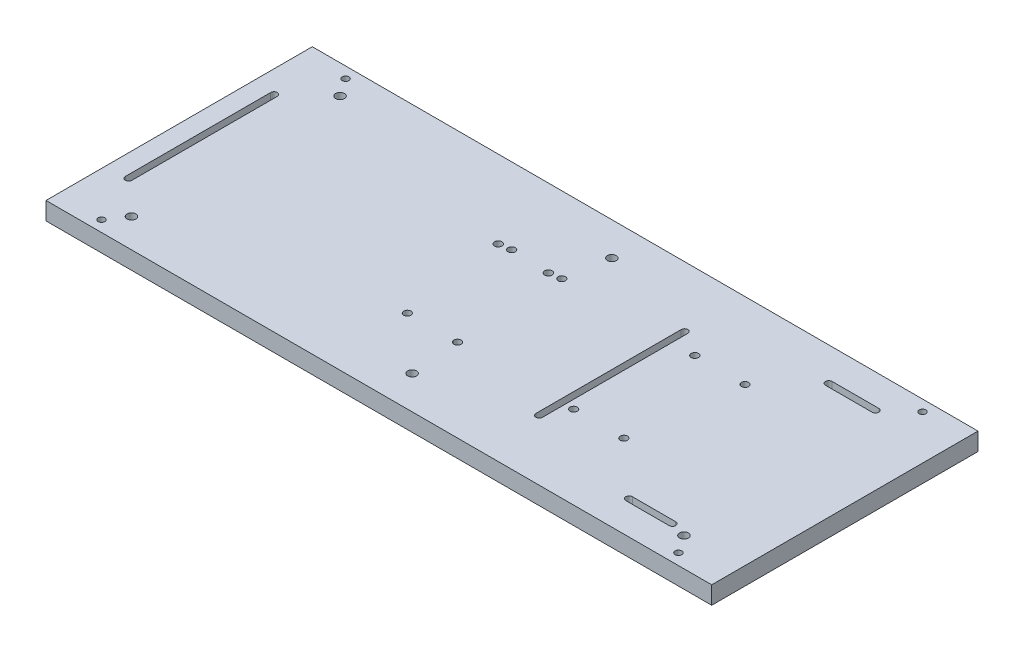
SolidWorks part; units mm, degrees
ref_plane "Front Plane" through (0, 0, 0) normal (0, 0, 1) x (1, 0, 0)
ref_plane "Top Plane" through (0, 0, 0) normal (0, 1, 0) x (1, 0, 0)
ref_plane "Right Plane" through (0, 0, 0) normal (1, 0, 0) x (0, 0, -1)
sketch "Sketch1" plane through (0, 0, 0) normal (0, 1, 0) x (1, 0, 0)
  line L1 (-66.9875, 84.7037) -> (233.0125, 84.7037)
  line L2 (-66.9875, 84.7037) -> (-66.9875, -35.2963)
  line L3 (-66.9875, -35.2963) -> (233.0125, -35.2963)
  line L4 (233.0125, 84.7037) -> (233.0125, -35.2963)
extrude "Boss-Extrude1" add sketch "Sketch1" along normal blind 8 contours L1 L4 L3 L2
sketch "Sketch2" plane through (0, 8, 0) normal (0, 1, 0) x (1, 0, 0)
  line L0 (-66.9875, 84.7037) -> (-46.9875, 84.7037) construction
  line L1 (-66.9875, 84.7037) -> (233.0125, 84.7037) construction
  line L2 (-66.9875, 84.7037) -> (-66.9875, 24.7037) construction
  line L3 (-66.9875, 84.7037) -> (-66.9875, -35.2963) construction
  line L4 (-66.9875, 24.7037) -> (12.7656, 24.7037) construction
  line L5 (-46.9875, 84.7037) -> (-46.9875, -35.2963) construction
  line L6 (-66.9875, -35.2963) -> (233.0125, -35.2963) construction
  line L7 (-46.9875, 24.7037) -> (-46.9875, 57.4537) construction
  line L8 (12.7656, 24.7037) -> (118.0125, 24.7037) construction
  line L9 (-46.9875, 57.4537) -> (118.0125, 57.4537)
  line L11 (-46.9875, -8.0463) -> (118.0125, -8.0463)
  line L12 (118.0125, 57.4537) -> (118.0125, -8.0463)
  line L13 (118.0125, 24.7037) -> (145.3738, 52.0649) construction
  line L14 (-46.9875, 57.4537) -> (-56.9875, 57.4537) construction
  line L15 (-56.9875, 57.4537) -> (-56.9875, -8.0463) construction
  line L16 (-56.9875, -8.0463) -> (-46.9875, -8.0463) construction
  line L18 (-58.4875, -8.0463) -> (-58.4875, 57.4537)
  line L19 (-55.4875, 57.4537) -> (-55.4875, -8.0463)
  line L20 (118.0125, 57.4537) -> (128.0125, 57.4537) construction
  line L21 (118.0125, -8.0463) -> (128.0125, -8.0463) construction
  line L22 (126.5125, -8.0463) -> (126.5125, 57.4537)
  line L23 (129.5125, 57.4537) -> (129.5125, -8.0463)
  circle A7 centre (79.7855, 50.3923) radius 1.636
  circle A8 centre (74.5023, 49.6303) radius 1.687
  circle A9 centre (81.0555, 2.1323) radius 1.636
  circle A12 centre (162.3355, 50.3923) radius 1.636
  circle A13 centre (155.9855, 2.1323) radius 1.636
  arc A14 (-55.4875, 57.4537) -> (-58.4875, 57.4537) centre (-56.9875, 57.4537) ccw
  arc A15 (-58.4875, -8.0463) -> (-55.4875, -8.0463) centre (-56.9875, -8.0463) ccw
  arc A16 (129.5125, 57.4537) -> (126.5125, 57.4537) centre (128.0125, 57.4537) ccw
  arc A17 (126.5125, -8.0463) -> (129.5125, -8.0463) centre (128.0125, -8.0463) ccw
  dimension "D1" = 45
extrude "Cut-Extrude1" cut sketch "Sketch2" against normal blind 8 contours A7 | A8 | A9 | A13
extrude "Cut-Extrude2" cut sketch "Sketch2<3>" against normal blind 8 contours L19 A15 L18 A14
sketch "Sketch2<3>" plane through (0, 8, 0) normal (0, 1, 0) x (1, 0, 0) same geometry as "Sketch2"
extrude "Cut-Extrude3" cut sketch "Sketch2<4>" against normal blind 8 contours L23 A17 L22 A16
sketch "Sketch2<4>" plane through (0, 8, 0) normal (0, 1, 0) x (1, 0, 0) same geometry as "Sketch2"
extrude "Cut-Extrude4" cut sketch "Sketch2<5>" against normal blind 8 contours A12
sketch "Sketch2<5>" plane through (0, 8, 0) normal (0, 1, 0) x (1, 0, 0) same geometry as "Sketch2"
sketch "Sketch5" plane through (0, 8, 0) normal (0, 1, 0) x (1, 0, 0)
  line L0 (-66.9875, 84.7037) -> (-56.9875, 84.7037) construction
  line L1 (-66.9875, 84.7037) -> (-46.9875, 84.7037) construction
  line L2 (-56.9875, 84.7037) -> (-56.9875, 74.7037) construction
  line L3 (-56.9875, 74.7037) -> (-66.9875, 74.7037) construction
  line L4 (-66.9875, 84.7037) -> (-66.9875, 24.7037) construction
  line L5 (-66.9875, -35.2963) -> (-66.9875, -25.2963) construction
  line L6 (-66.9875, 84.7037) -> (-66.9875, -35.2963) construction
  line L7 (-66.9875, -25.2963) -> (-56.9875, -25.2963) construction
  line L8 (233.0125, 84.7037) -> (223.0125, 84.7037) construction
  line L9 (-66.9875, 84.7037) -> (233.0125, 84.7037) construction
  line L10 (223.0125, 84.7037) -> (223.0125, 74.7037) construction
  line L11 (233.0125, -35.2963) -> (223.0125, -35.2963) construction
  line L12 (-66.9875, -35.2963) -> (233.0125, -35.2963) construction
  line L13 (223.0125, -35.2963) -> (223.0125, -25.2963) construction
  line L14 (233.0125, -35.2963) -> (83.0125, -35.2963) construction
  line L15 (-61.9875, -25.2963) -> (-61.9875, -30.2963) construction
  line L16 (83.0125, 84.7037) -> (83.0125, 69.7037) construction
  line L17 (83.0125, -35.2963) -> (83.0125, -20.2963) construction
  line L18 (228.0125, -35.2963) -> (228.0125, -30.2963) construction
  circle A2 centre (83.0125, 69.7037) radius 2
  circle A4 centre (83.0125, -20.2963) radius 2
  circle A6 centre (-61.9875, -30.2963) radius 1.5
  circle A7 centre (228.0125, -30.2963) radius 1.5
extrude "Cut-Extrude5" cut sketch "Sketch5" against normal blind 8 contours A4
extrude "Cut-Extrude6" cut sketch "Sketch5<3>" against normal blind 8 contours A2
sketch "Sketch5<3>" plane through (0, 8, 0) normal (0, 1, 0) x (1, 0, 0) same geometry as "Sketch5"
sketch "Sketch6" plane through (0, 8, 0) normal (0, 1, 0) x (1, 0, 0)
  line L0 (183.5918, 71.2037) -> (183.5918, 69.7037) construction
  line L2 (183.5918, -21.7963) -> (183.5918, -20.2963) construction
  line L4 (182.2685, -20.2963) -> (179.2685, -20.2963) construction
  line L5 (182.2685, 69.7037) -> (179.2685, 69.7037) construction
  line L6 (203.3034, 69.7037) -> (200.3034, 69.7037) construction
  line L7 (201.8034, -20.2963) -> (198.8034, -20.2963) construction
  line L8 (180.7685, 71.2037) -> (201.8034, 71.2037)
  line L9 (180.7685, 68.2037) -> (201.8034, 68.2037)
  line L10 (180.7685, -18.7963) -> (200.3034, -18.7963)
  line L11 (180.7685, -21.7963) -> (200.3034, -21.7963)
  arc A4 (180.7685, -18.7963) -> (180.7685, -21.7963) centre (180.7685, -20.2963) ccw
  arc A5 (200.3034, -21.7963) -> (200.3034, -18.7963) centre (200.3034, -20.2963) ccw
  arc A6 (180.7685, 71.2037) -> (180.7685, 68.2037) centre (180.7685, 69.7037) ccw
  arc A7 (201.8034, 68.2037) -> (201.8034, 71.2037) centre (201.8034, 69.7037) ccw
extrude "Cut-Extrude7" cut sketch "Sketch6" against normal blind 8
sketch "Sketch7" plane through (0, 8, 0) normal (0, 1, 0) x (1, 0, 0)
  line L1 (0, -35.2963) -> (0, -20.2963) construction
  line L2 (-66.9875, -35.2963) -> (233.0125, -35.2963) construction
  line L3 (0, 84.7037) -> (0, 69.7037) construction
  line L4 (-66.9875, 84.7037) -> (233.0125, 84.7037) construction
  line L5 (-66.9875, 84.7037) -> (0, 84.7037) construction
  line L6 (0, 84.7037) -> (66.99, 84.7037) construction
  line L7 (66.99, 84.7037) -> (66.99, -35.2963) construction
  line L9 (66.99, 84.7037) -> (233.0125, 84.7037) construction
  line L10 (150.0013, 84.7037) -> (150.0013, 72.736) construction
  line L11 (150.0013, 72.736) -> (150.0013, -27.264) construction
  spline S0 degree 2 poles (-66.9875, 84.7037) (0.0011, 54.7037) (66.99, 84.7037) knots 0 0 0 1 1 1
  spline S1 degree 2 poles (-66.9875, -35.2963) (0.0011, -5.2963) (66.99, -35.2963) knots 0 0 0 1 1 1
  spline S2 degree 2 poles (66.99, 84.7037) (150.0013, 60.7683) (233.0125, 84.7037) knots 0 0 0 1 1 1
  spline S3 degree 2 poles (66.99, -35.2963) (150.0013, -19.2317) (233.0125, -35.2963) knots 0 0 0 1 1 1
sketch "Sketch8" plane through (0, 8, 0) normal (0, 1, 0) x (1, 0, 0)
  line L0 (-66.9875, -35.2963) -> (-66.9875, -30.2963) construction
  line L1 (-66.9875, 84.7037) -> (-66.9875, -35.2963) construction
  line L2 (-66.9875, -30.2963) -> (-61.9875, -30.2963) construction
  line L3 (233.0125, -35.2963) -> (228.0125, -35.2963) construction
  line L4 (-66.9875, -35.2963) -> (233.0125, -35.2963) construction
  line L5 (228.0125, -35.2963) -> (228.0125, -30.2963) construction
  line L6 (233.0125, -30.2963) -> (213.0125, -30.2963) construction
  line L7 (233.0125, 84.7037) -> (233.0125, -35.2963) construction
  line L8 (-66.9875, -30.2963) -> (-46.9875, -30.2963) construction
  circle A3 centre (-46.9875, -30.2963) radius 1.5
  circle A4 centre (213.0125, -30.2963) radius 1.5
sketch "Sketch9" plane through (0, 0, 0) normal (0, -1, 0) x (1, 0, 0)
  line L0 (-66.9875, -84.7037) -> (-61.9875, -84.7037) construction
  line L1 (-66.9875, -84.7037) -> (233.0125, -84.7037) construction
  line L2 (-61.9875, -84.7037) -> (-61.9875, -79.7037) construction
  line L3 (233.0125, -84.7037) -> (227.7844, -84.7037) construction
  line L4 (227.7844, -84.7037) -> (227.7844, -79.7037) construction
  line L5 (-66.9875, -79.7037) -> (-46.9875, -79.7037) construction
  line L6 (-66.9875, -84.7037) -> (-66.9875, 35.2963) construction
  line L7 (233.0125, -79.7037) -> (213.0125, -79.7037) construction
  line L8 (233.0125, -84.7037) -> (233.0125, 35.2963) construction
  circle A2 centre (213.0125, -79.7037) radius 1.5
  circle A3 centre (-46.9875, -79.7037) radius 1.5
extrude "Cut-Extrude9" cut sketch "Sketch9" against normal blind 10 contours A2 | A3
extrude "Cut-Extrude10" cut sketch "Sketch8" against normal blind 10 contours A3 | A4
sketch "Sketch10" plane through (0, 0, 0) normal (0, -1, 0) x (1, 0, 0)
  line L0 (-66.9875, -84.7037) -> (-66.9875, -71.7037)
  line L1 (-66.9875, -84.7037) -> (-66.9875, 35.2963) construction
  line L2 (-66.9875, 35.2963) -> (-66.9875, 22.2963)
  line L3 (-66.9875, 22.2963) -> (-41.4875, 22.2963) construction
  line L4 (-66.9875, -71.7037) -> (-41.4875, -71.7037) construction
  line L5 (83.0125, -84.7037) -> (83.0125, 35.2963) construction
  line L6 (-66.9875, -84.7037) -> (233.0125, -84.7037) construction
  line L7 (-66.9875, 35.2963) -> (233.0125, 35.2963) construction
  line L8 (106.0328, 35.2963) -> (106.0328, -84.7037) construction
  line L9 (94.7194, 35.2963) -> (94.7194, -84.7037) construction
  circle A0 centre (-41.4875, 22.2963) radius 2
  circle A1 centre (-41.4875, -71.7037) radius 2
  circle A2 centre (155.9855, -2.1323) radius 1.636 construction
  circle A3 centre (162.3355, -50.3923) radius 1.636 construction
  circle A4 centre (79.7855, -50.3923) radius 1.636 construction
  circle A5 centre (74.5023, -49.6303) radius 1.687 construction
  circle A6 centre (81.0555, -2.1323) radius 1.636 construction
  circle A7 centre (155.9855, -2.1323) radius 1.636
  circle A8 centre (162.3355, -50.3923) radius 1.636
  circle A9 centre (79.7855, -50.3923) radius 1.636
  circle A10 centre (74.5023, -49.6303) radius 1.687
  circle A11 centre (81.0555, -2.1323) radius 1.636
  circle A17 centre (51.8753, -49.6303) radius 1.687
  circle A18 centre (57.1585, -50.3923) radius 1.636
  circle A19 centre (58.4285, -2.1323) radius 1.636
  circle A20 centre (139.7085, -50.3923) radius 1.636
  circle A21 centre (133.3585, -2.1323) radius 1.636
  circle A22 centre (207.5125, -71.7037) radius 2
  circle A23 centre (207.5125, 22.2963) radius 2
extrude "Cut-Extrude11" cut sketch "Sketch10" against normal blind 10 contours A20 | A21 | A18 | A17 | A19
extrude "Cut-Extrude12" cut sketch "Sketch10<3>" against normal blind 10 contours A23
sketch "Sketch10<3>" plane through (0, 0, 0) normal (0, -1, 0) x (1, 0, 0) same geometry as "Sketch10"
extrude "Cut-Extrude13" cut sketch "Sketch10<4>" against normal blind 10 contours A0 | A1
sketch "Sketch10<4>" plane through (0, 0, 0) normal (0, -1, 0) x (1, 0, 0) same geometry as "Sketch10"
